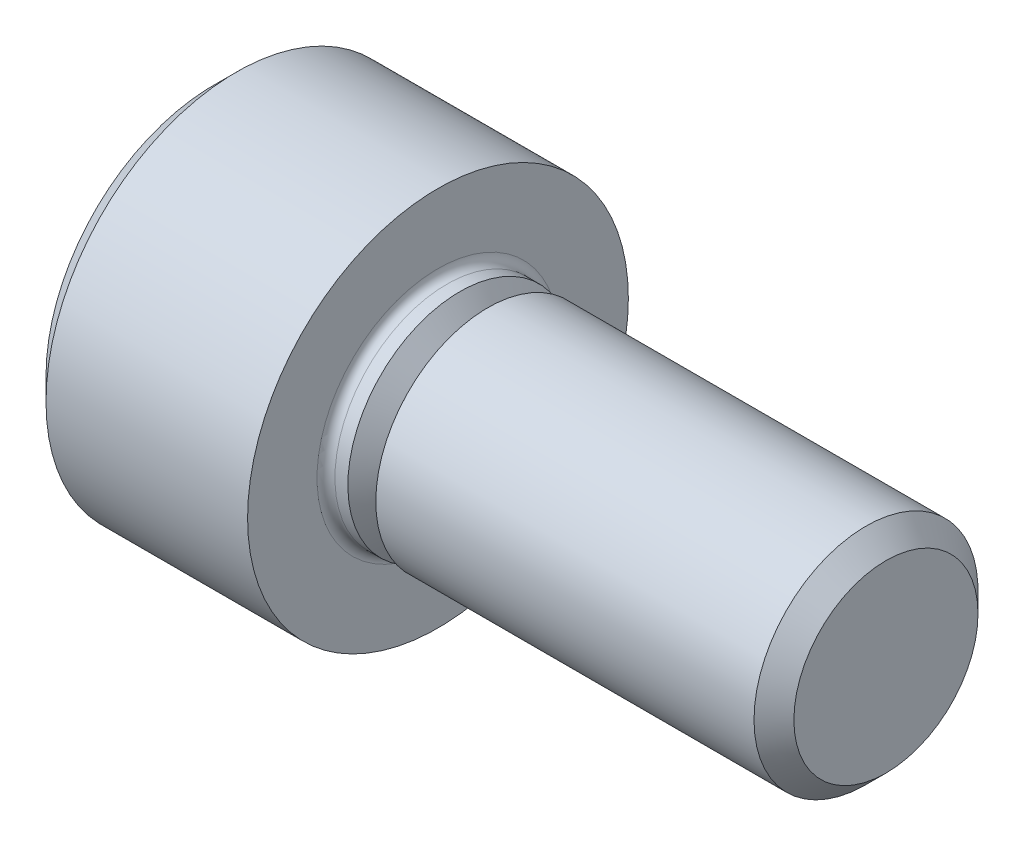
SolidWorks part; units mm, degrees
revolve "Base-Revolve" add sketch "BodySke"
sketch "BodySke" plane through (0, 0, 0) normal (0, 0, 1) x (1, 0, 0)
  line L0 (0, 0) -> (0, 3.75)
  line L1 (0.5, 4.25) -> (5, 4.25)
  line L2 (5, 4.25) -> (5, 2.5)
  line L3 (5, 2.5) -> (14.555, 2.5)
  line L4 (15, 2.055) -> (15, 0)
  line L5 (15, 0) -> (0, 0)
  line L6 (-31.75, 0) -> (127, 0) construction
  line L7 (0, 3.75) -> (0.5, 4.25)
  line L8 (15, 2.055) -> (14.555, 2.5)
  line L9 (0, -3.75) -> (0.5, -4.25) construction
  line L10 (15, -2.055) -> (14.555, -2.5) construction
  line L11 (5.8, 9.525) -> (5.8, 3.175) construction
  line L12 (-15, 9.525) -> (-15, 3.175) construction
  line L13 (-35, 9.525) -> (-35, 3.175) construction
  dimension "Diameter" = 5
  dimension "Head_ht" = 5
  dimension "Length" = 10
  dimension "Body_ch_ang" = 45
  dimension "Head_dia" = 8.5
  dimension "Head_ch_ang" = 45
  dimension "Minor_dia" = 4.11
  dimension "Advance" = 0.8
  dimension "Thread_nom" = 30
  dimension "Thread_length" = 50
  dimension "Head_ch_ht" = 0.5
cosmetic thread "ThreadCosmetic" [suppressed]
fillet "Fillet1" radius 0.2 1 edges at (5, 0, 2.5)
ref_plane "Plane1" through (0, 0, 0) normal (0, 0, 1) x (1, 0, 0)
ref_plane "Plane2" through (0, 0, 0) normal (0, 1, 0) x (1, 0, 0)
ref_plane "Plane3" through (0, 0, 0) normal (1, 0, 0) x (0, 0, -1)
sketch "Sketch2" plane through (0, 0, 0) normal (0, 0, 1) x (1, 0, 0)
  line L0 (0, 2.042) -> (2.5, 2.042)
  line L1 (2.5, 2.042) -> (3.6789, 0)
  line L2 (-31.75, 0) -> (127, 0) construction
  line L3 (3.6789, 0) -> (0, 0)
  line L4 (0, 0) -> (0, 2.042)
  line L5 (0, 3.75) -> (0, -3.75) construction
  line L6 (0, 0) -> (47.625, 0) construction
  line L7 (5, -4.25) -> (5, 4.25) construction
  dimension "D1" = 2.042
  dimension "D2" = 60
revolve "Hex-PreBroach" cut sketch "Sketch2" angle 360 about L6
sketch "Sketch3" plane through (0, 0, 0) normal (-1, 0, 0) x (0, 0.5, 0.866)
  line L0 (1.1789, 2.042) -> (-1.1789, 2.042)
  line L1 (-1.1789, 2.042) -> (-2.3579, 0)
  line L2 (1.1789, 2.042) -> (2.3579, 0)
  line L3 (1.1789, -2.042) -> (2.3579, 0)
  line L4 (1.1789, -2.042) -> (-1.1789, -2.042)
  line L5 (-1.1789, -2.042) -> (-2.3579, 0)
  dimension "D1" = 2.042
  dimension "D2" = 2.042
extrude "Hex" cut sketch "Sketch3" against normal blind 2.5
sketch "Sketch4" plane through (0, 0, 0) normal (-1, 0, 0) x (0, 0, 1)
  line L0 (0, 0) -> (2.3876, 0)
  line L1 (0, 0) -> (6.1484, 3.5498) construction
  line L2 (0, 0) -> (1.1938, 2.0677)
  line L3 (1.9883, 0.576) -> (2.2704, 0.7389)
  line L4 (1.493, 1.4339) -> (1.7751, 1.5968)
  arc A0 (1.9883, 0.576) -> (1.493, 1.4339) centre (0, 0) ccw
  arc A1 (2.3876, 0) -> (2.2704, 0.7389) centre (0, 0) ccw
  arc A2 (1.1938, 2.0677) -> (1.7751, 1.5968) centre (0, 0) cw
  dimension "D1" = 30
  dimension "D2" = 60
  dimension "Spline_p_dim" = 0.9906
  dimension "D3" = 0.4953
extrude "Spline" [suppressed] cut sketch "Sketch4" against normal blind 2.5
pattern_circular "CirPattern1" [suppressed] count 6 every 60
sketch "Sketch5" plane through (0, 0, 0) normal (0, 0, 1) x (1, 0, 0)
  line L0 (-31.75, 0) -> (127, 0) construction
  line L2 (0, 3.75) -> (0, -3.75) construction
  circle A0 centre (2, 0) radius 0.675
  dimension "Drilled_hole_dia" = 1.35
  dimension "Drilled_hole_loc" = 2
extrude "Hole" [suppressed] cut sketch "Sketch5" against normal through all and the other way through all
pattern_circular "Drilled-4" [suppressed] count 2 every 60
pattern_circular "Drilled-6" [suppressed] count 3 every 60
sketch "ThdSchSke" plane through (0, 0, 0) normal (0, 0, 1) x (1, 0, 0)
  line L0 (5.8, -2.055) -> (5.4884, -2.5)
  line L1 (5.8, -2.055) -> (6.1116, -2.5)
  line L2 (6.1116, -2.5) -> (6.1116, -3.125)
  line L3 (-3.175, 0) -> (5.1513, 0) construction
  line L5 (6.1116, -3.125) -> (5.4884, -3.125)
  line L6 (5.4884, -3.125) -> (5.4884, -2.5)
  line L7 (0, 3.75) -> (0, -3.75) construction
  dimension "Thread_minor" = 4.11
  dimension "Diameter" = 5
  dimension "Start" = 5.8
revolve "ThreadSchematic" cut sketch "ThdSchSke" angle 360 about L3
pattern_linear "ThdSchPat" rebuild error yes
equation "\"D2@Sketch3\" = \"Hex_size@Sketch3\" / 2"
equation "\"D1@Sketch3\" = \"Hex_size@Sketch3\" / 2"
equation "\"D1@Sketch2\" = \"Hex_size@Sketch3\" / 2"
equation "\"D3@Sketch4\" = \"Spline_p_dim@Sketch4\" / 2"
equation "\"Thread_minor@ThreadCosmetic\"  =  \"Minor_dia@BodySke\""
equation "\"D2@CirPattern1\" = 360 / \"Num_teeth@CirPattern1\""
equation "\"Wall_thickness@Sketch2\" = \"Head_ht@BodySke\" - \"Key_eng@Hex\""
equation "\"Thread_length@ThreadCosmetic\" = ((sgn( (\"Length@BodySke\" - \"Advance@BodySke\" ) - \"Thread_nom@BodySke\" )-1)*( (\"Length@BodySke\" - \"Advance@BodySke\" ) - \"Thread_nom@BodySke\" ))/-2+ \"Thread_nom@BodySke\""
equation "\"Thread_minor@ThdSchSke\" = \"Minor_dia@BodySke\""
equation "\"Diameter@ThdSchSke\" = \"Diameter@BodySke\""
equation "\"Overcut@ThdSchSke\" = \"Diameter@BodySke\" * 1.25"
equation "\"Start@ThdSchSke\" = \"Head_ht@BodySke\" + \"Length@BodySke\" - \"Thread_length@ThreadCosmetic\"  '---Non-countersunk---"
equation "\"Num_threads@ThdSchPat\" = int( \"Thread_length@ThreadCosmetic\" / \"Advance@BodySke\" + 0.999 )  + 1"
equation "\"Advance@ThdSchPat\" = \"Thread_length@ThreadCosmetic\" /  (\"Num_threads@ThdSchPat\" - 1) 'relax it"
equation "\"Num_threads@ThdSchPat\" = \"Num_threads@ThdSchPat\" - sgn( \"Num_threads@ThdSchPat\" - 1) '---chamfered tips only---"
